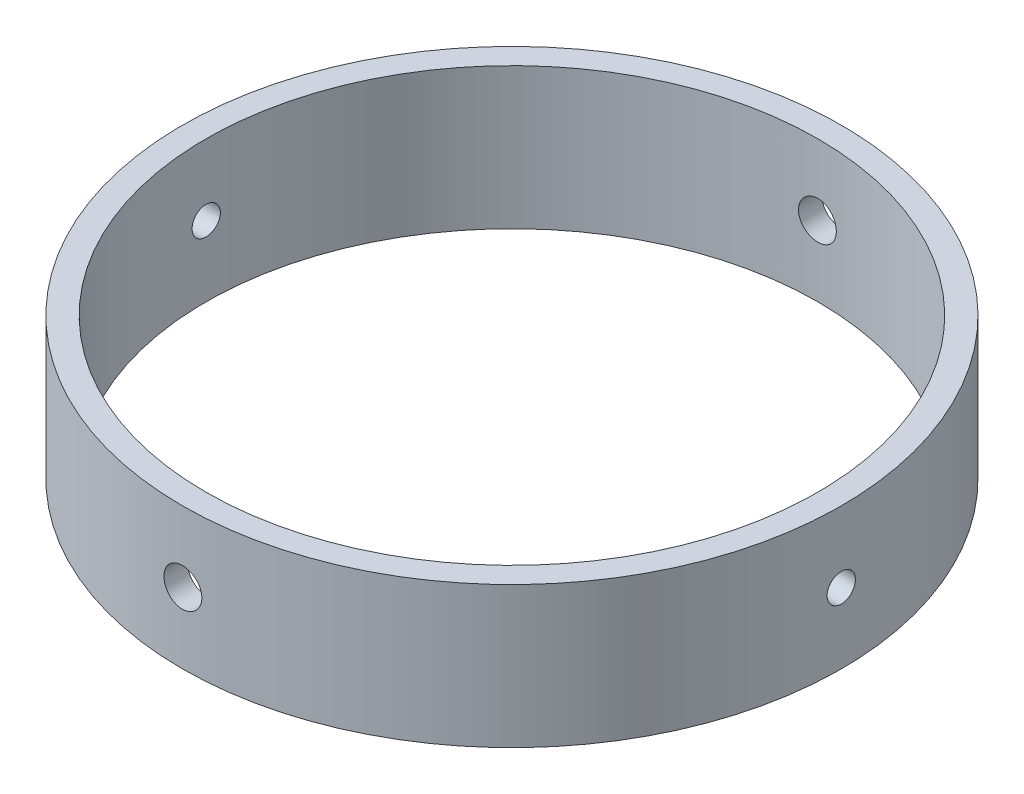
SolidWorks part; units mm, degrees
ref_plane "Front Plane" through (0, 0, 0) normal (0, 0, 1) x (1, 0, 0)
ref_plane "Top Plane" through (0, 0, 0) normal (0, 1, 0) x (1, 0, 0)
ref_plane "Right Plane" through (0, 0, 0) normal (1, 0, 0) x (0, 0, -1)
sketch "Sketch1" plane through (0, 0, 0) normal (0, 1, 0) x (1, 0, 0)
  circle A0 centre (0, 0) radius 44.45
  circle A1 centre (0, 0) radius 41.275
  dimension "D1" = 88.9
  dimension "D2" = 82.55
extrude "Boss-Extrude1" add sketch "Sketch1" along normal blind 19.05
ref_plane "Plane1" through (0, 0, 31.75) normal (0, 0, 1) x (1, 0, 0)
ref_plane "Plane2" through (0, 0, -31.75) normal (0, 0, 1) x (1, 0, 0)
sketch "Sketch3" plane through (0, 0, 31.75) normal (0, 0, 1) x (1, 0, 0)
  line L0 (41.275, 19.05) -> (-41.275, 19.05) construction
  circle A0 centre (0, 9.525) radius 2.7224
  dimension "D1" = 9.525
hole_wizard "Tap Drill for 1/4-20 Tap1" positions "Sketch4" profile "Sketch5" hole size "1/4-20" standard "ANSI Inch" end condition up to next
sketch "Sketch4" plane through (0, 0, 31.75) normal (0, 0, 1) x (1, 0, 0)
  point P0 (0, 9.525)
sketch "Sketch5" plane through (0, 9.525, 31.75) normal (1, 0, 0) x (0, -1, 0)
  line L0 (0, 0) -> (0, 76.2)
  line L1 (0, 76.2) -> (2.5527, 76.2)
  line L2 (2.5527, 76.2) -> (2.5527, 0)
  line L5 (2.5527, 0) -> (0, 0)
  line L11 (0, -6.35) -> (0, 107.95) construction
  dimension "Thru Hole Dia." = 5.1054
  dimension "Thru Hole Depth" = 76.2
sketch "Sketch7" plane through (0, 0, -31.75) normal (0, 0, 1) x (1, 0, 0)
  line L0 (44.45, 19.05) -> (-44.45, 19.05) construction
  circle A0 centre (0, 9.525) radius 3.5632
  dimension "D1" = 9.525
hole_wizard "Tap Drill for 1/4-20 Tap2" positions "Sketch8" profile "Sketch9" hole size "1/4-20" standard "ANSI Inch" end condition up to next
sketch "Sketch8" plane through (0, 0, -31.75) normal (0, 0, 1) x (1, 0, 0)
  point P0 (0, 9.525)
sketch "Sketch9" plane through (0, 9.525, -31.75) normal (1, 0, 0) x (0, 1, 0)
  line L0 (0, 0) -> (0, 76.2)
  line L1 (0, 76.2) -> (2.5527, 76.2)
  line L2 (2.5527, 76.2) -> (2.5527, 0)
  line L5 (2.5527, 0) -> (0, 0)
  line L11 (0, -6.35) -> (0, 107.95) construction
  dimension "Thru Hole Dia." = 5.1054
  dimension "Thru Hole Depth" = 76.2
ref_plane "Plane3" through (31.75, 0, 0) normal (1, 0, 0) x (0, 0, -1)
ref_plane "Plane4" through (-31.75, 0, 0) normal (1, 0, 0) x (0, 0, -1)
sketch "Sketch10" plane through (-31.75, 0, 0) normal (1, 0, 0) x (0, 0, -1)
  circle A0 centre (0, 9.4879) radius 1.905
  dimension "D1" = 3.81
extrude "Cut-Extrude3" cut sketch "Sketch10" against normal through all and the other way through all
sketch3d "3DSketch1"
  point P0 (40.508, 8.9339, 18.3005)
